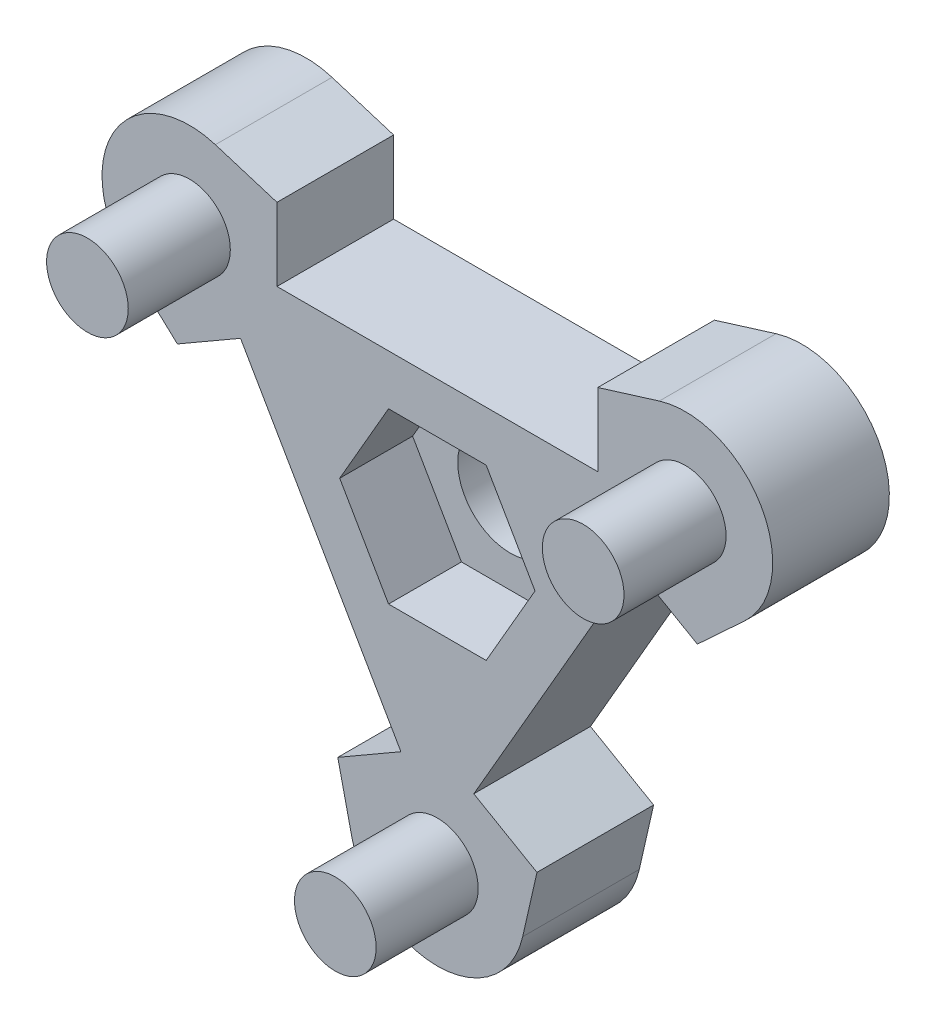
SolidWorks part; units mm, degrees
ref_plane "正面" through (0, 0, 0) normal (0, 0, 1) x (1, 0, 0)
ref_plane "平面" through (0, 0, 0) normal (0, 1, 0) x (1, 0, 0)
ref_plane "右側面" through (0, 0, 0) normal (1, 0, 0) x (0, 0, -1)
sketch "ｽｹｯﾁ1" plane through (0, 0, 0) normal (0, 0, 1) x (1, 0, 0)
  line L0 (-6.75, 2.4537) -> (-8.9151, 1.2037)
  line L1 (0, -9.2376) -> (8, 4.6188) construction
  line L2 (8, 4.6188) -> (-8, 4.6188) construction
  line L3 (-8, 4.6188) -> (0, -9.2376) construction
  line L4 (8.5, 4.9075) -> (-8.5, 4.9075) construction
  line L5 (-8.5, 4.9075) -> (0, -9.815) construction
  line L6 (0, -9.815) -> (8.5, 4.9075) construction
  line L7 (-8.9151, 1.2037) -> (-10.5379, 2.7059)
  line L8 (-1.25, -7.0725) -> (-3.4151, -8.3225)
  line L9 (-3.4151, -8.3225) -> (-2.9256, -10.479)
  line L10 (-8.9151, 1.2037) -> (-3.4151, -8.3225) construction
  line L11 (5.5, 7.1188) -> (7.6123, 7.7731)
  line L12 (5.5, 4.6188) -> (5.5, 7.1188)
  line L13 (-5.5, 7.1188) -> (-7.6123, 7.7731)
  line L14 (-5.5, 4.6188) -> (-5.5, 7.1188)
  line L15 (3.4151, -8.3225) -> (2.9256, -10.479)
  line L16 (1.25, -7.0725) -> (3.4151, -8.3225)
  line L17 (8.9151, 1.2037) -> (10.5379, 2.7059)
  line L18 (6.75, 2.4537) -> (8.9151, 1.2037)
  line L19 (-6.75, 2.4537) -> (-1.25, -7.0725)
  line L20 (1.25, -7.0725) -> (6.75, 2.4537)
  line L21 (5.5, 4.6188) -> (-5.5, 4.6188)
  circle A0 centre (0, 0) radius 4.6188 construction
  circle A1 centre (0, 0) radius 4.9075 construction
  arc A2 (-7, 2.3094) -> (-6.757, 2.4658) centre (-8.5, 4.9075) ccw
  arc A3 (1.5, -7.2169) -> (1.243, -7.0846) centre (0, -9.815) ccw
  arc A4 (5.5, 4.9075) -> (5.5139, 4.6188) centre (8.5, 4.9075) ccw
  arc A5 (-7.6123, 7.7731) -> (-10.5379, 2.7059) centre (-8.5, 4.9075) ccw
  arc A6 (10.5379, 2.7059) -> (7.6123, 7.7731) centre (8.5, 4.9075) ccw
  arc A7 (-2.9256, -10.479) -> (2.9256, -10.479) centre (0, -9.815) ccw
  arc A8 (-5.5139, 4.6188) -> (-5.5, 4.9075) centre (-8.5, 4.9075) ccw
  arc A9 (6.757, 2.4658) -> (7, 2.3094) centre (8.5, 4.9075) ccw
  arc A10 (-1.243, -7.0846) -> (-1.5, -7.2169) centre (0, -9.815) ccw
  point P19 (-4, -2.3094)
  point P34 (0, 0)
  dimension "D3" = 6
  dimension "D1" = 16
  dimension "D2" = 17
  dimension "D4" = 11
  dimension "D5" = 5.5
  dimension "D6" = 2.5
  dimension "D7" = 3
extrude "ﾎﾞｽ - 押し出し1" add sketch "ｽｹｯﾁ1" along normal blind 4 contours L9 A7 L15 L16 L20 L18 L17 A6 L11 L12 L21 L14 L13 A5 L7 L0 L19 L8 region at (0, 0, 0)
sketch "ｽｹｯﾁ2" plane through (0, 0, 4) normal (0, 0, 1) x (1, 0, 0)
  circle A0 centre (-8.5, 4.9075) radius 1.4
  circle A1 centre (0, -9.815) radius 1.4
  circle A2 centre (8.5, 4.9075) radius 1.4
  dimension "D1" = 2.8
extrude "ﾎﾞｽ - 押し出し2" add sketch "ｽｹｯﾁ2" along normal blind 3.5
sketch "ｽｹｯﾁ4" plane through (0, 0, 4) normal (0, 0, 1) x (1, 0, 0)
  line L1 (-1.6743, -2.9) -> (1.6743, -2.9)
  line L2 (1.6743, -2.9) -> (3.3486, 0)
  line L3 (3.3486, 0) -> (1.6743, 2.9)
  line L4 (1.6743, 2.9) -> (-1.6743, 2.9)
  line L5 (-1.6743, 2.9) -> (-3.3486, 0)
  line L6 (-3.3486, 0) -> (-1.6743, -2.9)
  circle A0 centre (0, 0) radius 2.9 construction
  dimension "D1" = 5.8
extrude "ｶｯﾄ - 押し出し1" cut sketch "ｽｹｯﾁ4" against normal blind 2.5
sketch "ｽｹｯﾁ6" plane through (0, 0, 0) normal (0, 0, -1) x (-1, 0, 0)
  circle A0 centre (0, 0) radius 1.8
  dimension "D1" = 3.6
extrude "ｶｯﾄ - 押し出し2" cut sketch "ｽｹｯﾁ6" against normal through all
equation "\"D5@ｽｹｯﾁ1\"=\"D4@ｽｹｯﾁ1\"/2"
